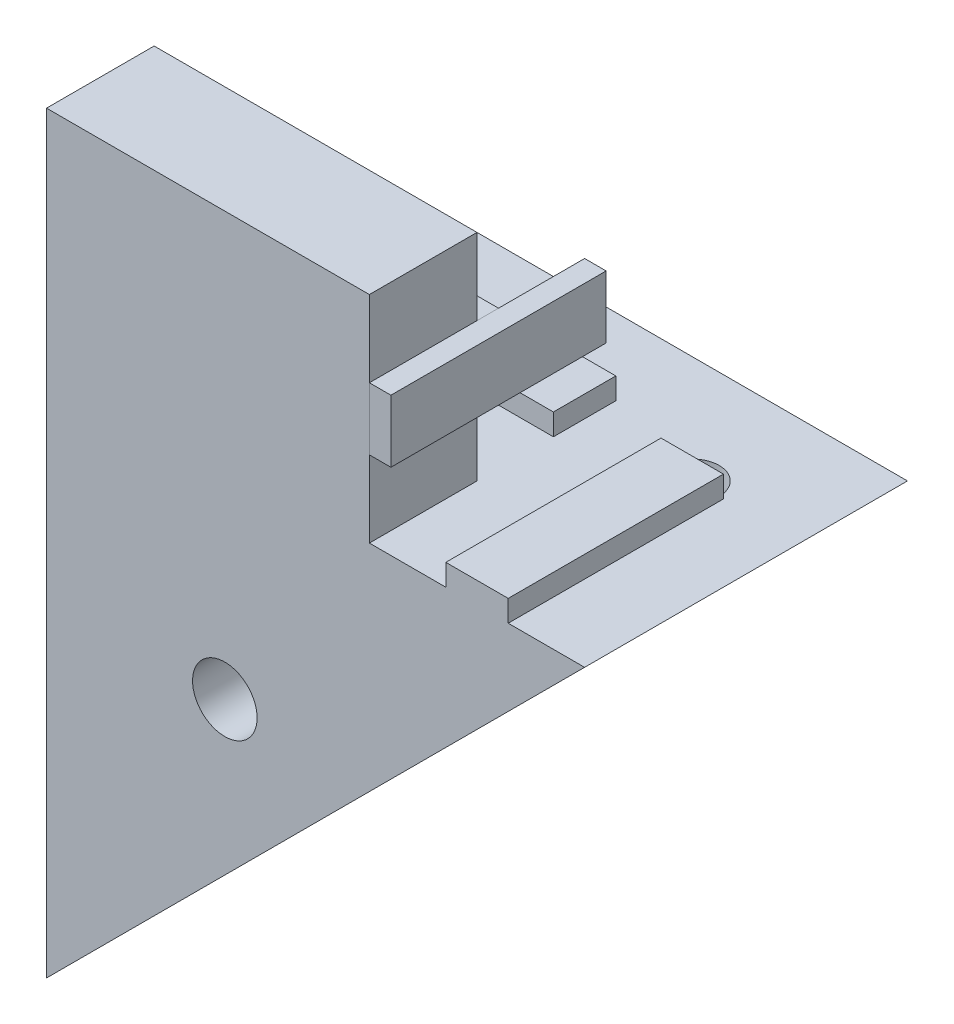
SolidWorks part; units mm, degrees
ref_plane "Front Plane" through (0, 0, 0) normal (0, 0, 1) x (1, 0, 0)
ref_plane "Top Plane" through (0, 0, 0) normal (0, 1, 0) x (1, 0, 0)
ref_plane "Right Plane" through (0, 0, 0) normal (1, 0, 0) x (0, 0, -1)
ref_plane "FrontPlane+10mm" through (0, 0, 10) normal (0, 0, 1) x (1, 0, 0)
sketch "Sketch1" plane through (0, 0, 0) normal (0, 0, 1) x (1, 0, 0)
  line L0 (-290, 0) -> (-10, 0) construction
  line L1 (0, 0) -> (-90, -90) construction
  line L2 (-10, 0) -> (0, 0) construction
  line L3 (-10, 0) -> (-10, 10) construction
  line L4 (-10, 10) -> (0, 10) construction
  line L5 (0, 0) -> (0, 10) construction
  line L6 (-90, -90) -> (-210, -90) construction
  line L7 (-300, 10) -> (-290, 10) construction
  line L8 (-300, 10) -> (-300, 0) construction
  line L9 (0, 0) -> (-10, 0)
  line L10 (-290, 10) -> (-290, 0) construction
  line L11 (-210, -90) -> (-300, 0) construction
  line L12 (-87.4264, -73.2843) -> (-16.7157, -2.5736) construction
  line L13 (-100, -80) -> (-90, -80) construction
  line L14 (-100, -80) -> (-100, -90) construction
  line L15 (-10, 0) -> (-10, 10)
  line L16 (-90, -80) -> (-90, -90) construction
  line L17 (-16.7157, -2.5736) -> (-9.6447, -9.6447) construction
  line L18 (-87.4264, -73.2843) -> (-80.3553, -80.3553) construction
  line L19 (-16.7157, -2.5736) -> (0, 0) construction
  line L20 (-87.4264, -73.2843) -> (-90, -90) construction
  line L21 (-10, 10) -> (-25, 10)
  line L22 (0, 0) -> (-9.6447, -9.6447)
  line L23 (-9.6447, -9.6447) -> (-16.7157, -2.5736)
  line L24 (-16.7157, -2.5736) -> (-25, -10.8579)
  line L25 (-25, -10.8579) -> (-25, 10)
  dimension "D1" = 10
  dimension "D2" = 10
  dimension "D3" = 300
  dimension "D4" = 10
  dimension "D5" = 120
  dimension "D6" = 135
  dimension "D7" = 45
  dimension "D8" = 45
  dimension "D9" = 127.2792
  dimension "D10" = 10
  dimension "D11" = 10
  dimension "D12" = 10
  dimension "D13" = 100
  dimension "D14" = 25
extrude "Main" add sketch "Sketch1" along normal blind 15
sketch "Sketch4" plane through (0, 0, 0) normal (0, 0, -1) x (-1, 0, 0)
  line L1 (10, 0) -> (25, 0)
  line L2 (10, 0) -> (10, 10)
  line L3 (10, 10) -> (25, 10)
  line L4 (25, 0) -> (25, 10)
extrude "Cut-Extrude2" cut sketch "Sketch4" against normal blind 10
sketch "Sketch2" plane through (0, 0, 10) normal (0, 0, -1) x (-1, 0, 0)
  line L0 (10, 0) -> (10, 10) construction
  line L1 (10, 6.45) -> (25, 6.45)
  line L2 (10, 6.45) -> (10, 3.55)
  line L3 (10, 3.55) -> (25, 3.55)
  line L4 (25, 6.45) -> (25, 3.55)
  line L5 (25, 0) -> (25, -10.8579) construction
  line L6 (10, 10) -> (25, 10) construction
  dimension "D1" = 3.55
  dimension "D2" = 2.9
extrude "Boss-Extrude3" add sketch "Sketch2" along normal blind 1
sketch "Sketch5" plane through (-7.0711, 7.0711, 0) normal (0.7071, -0.7071, 0) x (0, 0, -1)
  line L0 (-15, -25.3553) -> (0, -25.3553) construction
  line L1 (-3.55, -25.3553) -> (-6.45, -25.3553)
  line L2 (-3.55, -25.3553) -> (-3.55, -13.6396)
  line L3 (-3.55, -13.6396) -> (-6.45, -13.6396)
  line L4 (-6.45, -25.3553) -> (-6.45, -13.6396)
  line L5 (-15, -13.6396) -> (0, -13.6396) construction
  line L6 (0, -25.3553) -> (0, -13.6396) construction
  dimension "D1" = 3.55
  dimension "D2" = 2.9
extrude "Boss-Extrude4" add sketch "Sketch5" along normal blind 1
sketch "Sketch6" plane through (0, 0, 10) normal (0, 0, 1) x (1, 0, 0)
  line L0 (-25, -10.8579) -> (-16.7157, -2.5736)
  line L1 (-16.7157, -2.5736) -> (-9.6447, -9.6447)
  line L2 (-9.6447, -9.6447) -> (-25, -25)
  line L3 (-25, -10.8579) -> (-25, -25)
  line L4 (-13.1802, -6.1091) -> (-20.2513, -13.1802) construction
  circle A0 centre (-16.7157, -9.6447) radius 1.5
  point P13 (-16.7157, -9.6447)
  dimension "D1" = 3
  dimension "D2" = 21.7157
  dimension "D3" = 14.1421
  dimension "D4" = 5
extrude "Boss-Extrude5" add sketch "Sketch6" along normal blind 5
sketch "Sketch7" plane through (0, 0, 10) normal (0, 0, -1) x (-1, 0, 0)
  line L0 (14.2055, -5.0838) -> (25, -15.8783)
  line L1 (25, -10.8579) -> (25, -25) construction
  line L3 (25, -15.8783) -> (25, -19.9795)
  line L4 (25, -19.9795) -> (12.1549, -7.1344)
  line L5 (12.1549, -7.1344) -> (14.2055, -5.0838)
  line L7 (9.6447, -9.6447) -> (16.7157, -2.5736) construction
  line L8 (16.7157, -2.5736) -> (9.6447, -9.6447) construction
  line L10 (25, -25) -> (0, 0) construction
  point P8 (15.2239, -13.4218)
  dimension "D1" = 2.9
  dimension "D2" = 3.55
extrude "Boss-Extrude6" add sketch "Sketch7" along normal blind 1
sketch "Sketch8" plane through (0, 0, 0) normal (0, 1, 0) x (1, 0, 0)
  line L0 (0, -15) -> (-10, -15) construction
  line L1 (-3.55, -15) -> (-6.45, -15)
  line L2 (-3.55, -15) -> (-3.55, -5)
  line L3 (-3.55, -5) -> (-6.45, -5)
  line L4 (-6.45, -15) -> (-6.45, -5)
  line L5 (0, -15) -> (0, 0) construction
  dimension "D1" = 3.55
  dimension "D2" = 2.9
  dimension "D3" = 10
extrude "Boss-Extrude7" add sketch "Sketch8" along normal blind 1
sketch "Sketch9" plane through (0, 0, 15) normal (0, 0, 1) x (1, 0, 0)
  line L0 (-10, 0) -> (-10, 10) construction
  line L1 (-10, 6.45) -> (-9, 6.45)
  line L2 (-10, 6.45) -> (-10, 3.55)
  line L3 (-10, 3.55) -> (-9, 3.55)
  line L4 (-9, 6.45) -> (-9, 3.55)
  line L5 (-10, 10) -> (-25, 10) construction
  dimension "D1" = 1
  dimension "D2" = 3.55
  dimension "D3" = 2.9
extrude "Boss-Extrude8" add sketch "Sketch9" against normal blind 10 separate body
sketch "Sketch11" plane through (0, 0, 0) normal (0, 1, 0) x (1, 0, 0)
  line L0 (0, -15) -> (0, 0) construction
  line L1 (0, 0) -> (-25, 0) construction
  circle A0 centre (-5, -5) radius 1.25
  dimension "D1" = 2.5
  dimension "D2" = 5
  dimension "D3" = 5
extrude "Cut-Extrude4" cut sketch "Sketch11" against normal through all
sketch "Sketch12" plane through (0, 0, 15) normal (0, 0, 1) x (1, 0, 0)
  circle A0 centre (-16.7157, -9.6447) radius 1.5
  arc A1 (-15.4189, -10.3984) -> (-17.4695, -8.3478) centre (-16.7157, -9.6447) ccw construction
extrude "Cut-Extrude5" cut sketch "Sketch12" against normal through all
sketch "Sketch13" plane through (0, 0, 0) normal (0, 1, 0) x (1, 0, 0)
  line L0 (-25, -10) -> (-25, 0) construction
  line L1 (-10, -3.55) -> (-25, -3.55)
  line L2 (-10, -3.55) -> (-10, -6.45)
  line L3 (-10, -6.45) -> (-25, -6.45)
  line L4 (-25, -3.55) -> (-25, -6.45)
  line L5 (0, -15) -> (0, 0) construction
  line L6 (0, 0) -> (-25, 0) construction
  dimension "D1" = 10
  dimension "D2" = 2.9
  dimension "D3" = 3.55
extrude "Boss-Extrude9" add sketch "Sketch13" along normal blind 1
